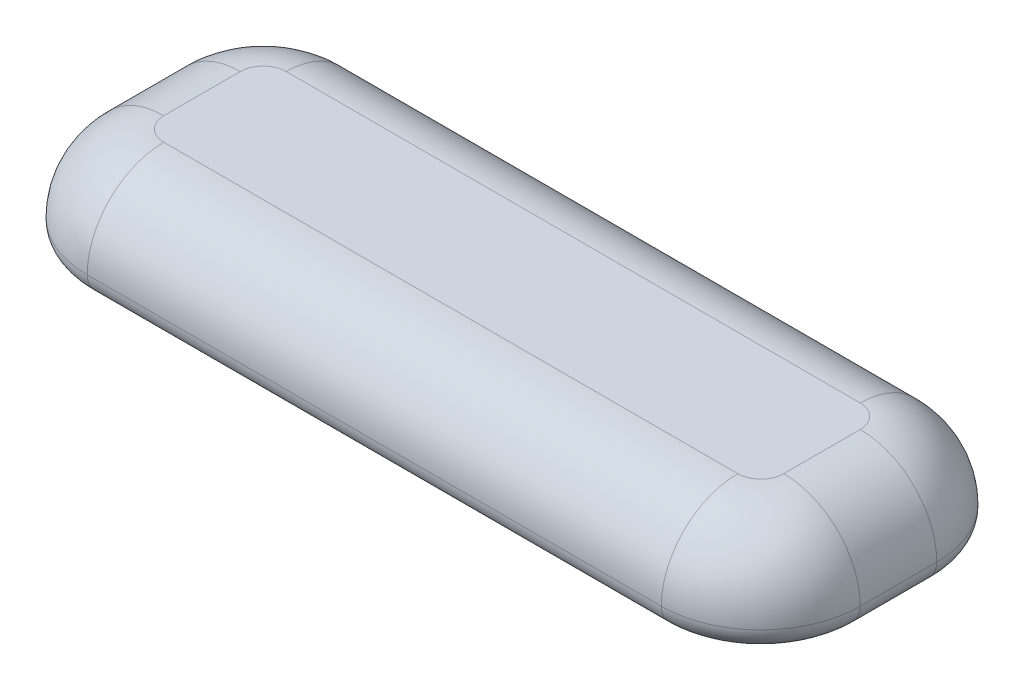
SolidWorks part; units mm, degrees
ref_plane "前视基准面" through (0, 0, 0) normal (0, 0, 1) x (1, 0, 0)
ref_plane "上视基准面" through (0, 0, 0) normal (0, 1, 0) x (1, 0, 0)
ref_plane "右视基准面" through (0, 0, 0) normal (1, 0, 0) x (0, 0, -1)
sketch "草图1" plane through (0, 0, 0) normal (0, 1, 0) x (1, 0, 0)
  line L1 (-37.5, 15) -> (37.5, 15)
  line L2 (-47.5, 5) -> (-47.5, -5)
  line L3 (-37.5, -15) -> (37.5, -15)
  line L4 (47.5, 5) -> (47.5, -5)
  line L5 (0, -15) -> (0, 15) construction
  line L6 (-47.5, 0) -> (47.5, 0) construction
  arc A0 (-47.5, -5) -> (-37.5, -15) centre (-37.5, -5) ccw
  arc A1 (-47.5, 5) -> (-37.5, 15) centre (-37.5, 5) cw
  arc A2 (37.5, 15) -> (47.5, 5) centre (37.5, 5) cw
  arc A3 (47.5, -5) -> (37.5, -15) centre (37.5, -5) cw
  point P0 (0, 0)
  point P8 (-47.5, 15)
  point P11 (47.5, 15)
  point P15 (47.5, -15)
  dimension "D3" = 10
  dimension "D1" = 95
  dimension "D2" = 30
extrude "凸台-拉伸1" add sketch "草图1" along normal blind 10
shell "抽壳2" thickness 3 removed face at (0, 0, 0) outward yes
fillet "圆角3" radius 10 8 edges at (46.6924, 13, -14.1924) (50.5, 13, 0) (46.6924, 13, 14.1924) (0, 13, 18) (-46.6924, 13, 14.1924) (-50.5, 13, 0) (-46.6924, 13, -14.1924) (0, 13, -18)
fillet "圆角4" radius 3 8 edges at (50.5, 0, 0) (46.6924, 0, 14.1924) (0, 0, 18) (-46.6924, 0, 14.1924) (-50.5, 0, 0) (-46.6924, 0, -14.1924) (0, 0, -18) (46.6924, 0, -14.1924)
ref_plane "基准面1" through (0, 10, 0) normal (0, -1, 0) x (-1, 0, 0)
sketch "草图2" plane through (0, 10, 0) normal (0, -1, 0) x (-1, 0, 0)
  line L0 (0, 0) -> (36.8, 0) construction
  line L1 (0, 0) -> (0, 6.5357) construction
  line L2 (34.725, 0.575) -> (38.875, 0.575)
  line L3 (34.725, 0.575) -> (34.725, -0.575)
  line L4 (34.725, -0.575) -> (38.875, -0.575)
  line L5 (38.875, 0.575) -> (38.875, -0.575)
  line L6 (36.8, -0.575) -> (36.8, 0.575) construction
  line L7 (34.725, 0) -> (38.875, 0) construction
  line L8 (36.225, 2.075) -> (37.375, 2.075)
  line L9 (36.225, 2.075) -> (36.225, -2.075)
  line L10 (36.225, -2.075) -> (37.375, -2.075)
  line L11 (37.375, 2.075) -> (37.375, -2.075)
  line L12 (36.8, -2.075) -> (36.8, 2.075) construction
  line L13 (36.225, 0) -> (37.375, 0) construction
  line L14 (-36.225, 0) -> (-37.375, 0) construction
  line L15 (-36.8, -2.075) -> (-36.8, 2.075) construction
  line L16 (-34.725, 0) -> (-38.875, 0) construction
  line L17 (-36.8, -0.575) -> (-36.8, 0.575) construction
  line L18 (-37.375, 2.075) -> (-37.375, -2.075)
  line L19 (-36.225, -2.075) -> (-37.375, -2.075)
  line L20 (-36.225, 2.075) -> (-36.225, -2.075)
  line L21 (-36.225, 2.075) -> (-37.375, 2.075)
  line L22 (-38.875, 0.575) -> (-38.875, -0.575)
  line L23 (-34.725, -0.575) -> (-38.875, -0.575)
  line L24 (-34.725, 0.575) -> (-34.725, -0.575)
  line L25 (-34.725, 0.575) -> (-38.875, 0.575)
  circle A0 centre (36.8, 0) radius 2.675
  circle A1 centre (-36.8, 0) radius 2.675
  dimension "D2" = 5.35
  dimension "D1" = 36.8
  dimension "D3" = 4.15
  dimension "D4" = 1.15
  dimension "D5" = 4.15
  dimension "D6" = 1.15
extrude "凸台-拉伸2" add sketch "草图2" along normal blind 8 contours A0 L8 L11 L2 L5 L4 L10 L9 L3 | A1 L25 L24 L23 L20 L19 L18 L22 L21 region at (-34.2007, 10, 0) region at (39.3993, 10, 0)
sketch "草图3" plane through (0, 10, 0) normal (0, -1, 0) x (1, 0, 0)
  line L12 (-37.375, -2.075) -> (-36.225, -2.075)
  line L13 (-36.225, -2.075) -> (-36.225, -0.575)
  line L14 (-36.225, -0.575) -> (-34.725, -0.575)
  line L15 (-34.725, -0.575) -> (-34.725, 0.575)
  line L16 (-34.725, 0.575) -> (-36.225, 0.575)
  line L17 (-36.225, 0.575) -> (-36.225, 2.075)
  line L18 (-36.225, 2.075) -> (-37.375, 2.075)
  line L19 (-37.375, 2.075) -> (-37.375, 0.575)
  line L20 (-37.375, 0.575) -> (-38.875, 0.575)
  line L21 (-38.875, 0.575) -> (-38.875, -0.575)
  line L22 (-38.875, -0.575) -> (-37.375, -0.575)
  line L23 (-37.375, -0.575) -> (-37.375, -2.075)
  line L24 (-37.375, -2.075) -> (-36.225, -2.075)
  line L25 (-36.225, -2.075) -> (-36.225, -0.575)
  line L26 (-36.225, -0.575) -> (-34.725, -0.575)
  line L27 (-34.725, -0.575) -> (-34.725, 0.575)
  line L28 (-34.725, 0.575) -> (-36.225, 0.575)
  line L29 (-36.225, 0.575) -> (-36.225, 2.075)
  line L30 (-36.225, 2.075) -> (-37.375, 2.075)
  line L31 (-37.375, 2.075) -> (-37.375, 0.575)
  line L32 (-37.375, 0.575) -> (-38.875, 0.575)
  line L33 (-38.875, 0.575) -> (-38.875, -0.575)
  line L34 (-38.875, -0.575) -> (-37.375, -0.575)
  line L35 (-37.375, -0.575) -> (-37.375, -2.075)
  line L36 (34.725, 0.575) -> (34.725, -0.575)
  line L37 (34.725, -0.575) -> (36.225, -0.575)
  line L38 (36.225, -0.575) -> (36.225, -2.075)
  line L39 (36.225, -2.075) -> (37.375, -2.075)
  line L40 (37.375, -2.075) -> (37.375, -0.575)
  line L41 (37.375, -0.575) -> (38.875, -0.575)
  line L42 (38.875, -0.575) -> (38.875, 0.575)
  line L43 (38.875, 0.575) -> (37.375, 0.575)
  line L44 (37.375, 0.575) -> (37.375, 2.075)
  line L45 (37.375, 2.075) -> (36.225, 2.075)
  line L46 (36.225, 2.075) -> (36.225, 0.575)
  line L47 (36.225, 0.575) -> (34.725, 0.575)
  line L48 (34.725, 0.575) -> (34.725, -0.575)
  line L49 (34.725, -0.575) -> (36.225, -0.575)
  line L50 (36.225, -0.575) -> (36.225, -2.075)
  line L51 (36.225, -2.075) -> (37.375, -2.075)
  line L52 (37.375, -2.075) -> (37.375, -0.575)
  line L53 (37.375, -0.575) -> (38.875, -0.575)
  line L54 (38.875, -0.575) -> (38.875, 0.575)
  line L55 (38.875, 0.575) -> (37.375, 0.575)
  line L56 (37.375, 0.575) -> (37.375, 2.075)
  line L57 (37.375, 2.075) -> (36.225, 2.075)
  line L58 (36.225, 2.075) -> (36.225, 0.575)
  line L59 (36.225, 0.575) -> (34.725, 0.575)
  dimension "D1" = 0
  dimension "D2" = 0
extrude "凸台-拉伸3" add sketch "草图3" along normal blind 4
fillet "圆角11" radius 0.3 8 edges at (37.375, 4, -0.575) (36.225, 4, -0.575) (36.225, 4, 0.575) (37.375, 4, 0.575) (-37.375, 4, -0.575) (-36.225, 4, -0.575) (-36.225, 4, 0.575) (-37.375, 4, 0.575)
fillet "圆角7" radius 5 8 edges at (0, 10, 15) (44.5711, 10, 12.0711) (47.5, 10, 0) (44.5711, 10, -12.0711) (0, 10, -15) (-44.5711, 10, -12.0711) (-47.5, 10, 0) (-44.5711, 10, 12.0711)
chamfer "倒角1" distance 0.2 angle 45 16 edges at (36.8, 2, -2.075) (36.225, 2, -1.475) (35.325, 2, -0.575) (34.725, 2, 0) (35.325, 2, 0.575) (36.225, 2, 1.475) (36.8, 2, 2.075) (37.375, 2, 1.475) (38.275, 2, 0.575) (38.875, 2, 0) (38.275, 2, -0.575) (37.375, 2, -1.475) (36.1371, 2, 0.6629) (37.4629, 2, 0.6629) (36.1371, 2, -0.6629) (37.4629, 2, -0.6629)
chamfer "倒角2" distance 0.2 angle 45 16 edges at (-36.225, 2, -1.475) (-35.325, 2, -0.575) (-34.725, 2, 0) (-35.325, 2, 0.575) (-36.225, 2, 1.475) (-36.8, 2, 2.075) (-37.375, 2, 1.475) (-38.275, 2, 0.575) (-38.875, 2, 0) (-38.275, 2, -0.575) (-37.375, 2, -1.475) (-36.8, 2, -2.075) (-36.1371, 2, -0.6629) (-36.1371, 2, 0.6629) (-37.4629, 2, 0.6629) (-37.4629, 2, -0.6629)
fillet "圆角9" radius 5 1 edges at (36.8, 10, -2.675) second distance 5.5 conic rho 0.25 first distance on face at (36.8, 2, -2.675)
fillet "圆角10" radius 5 1 edges at (-36.8, 10, 2.675) second distance 5.5 conic rho 0.25 first distance on face at (-0.2815, 10, -1.25)
